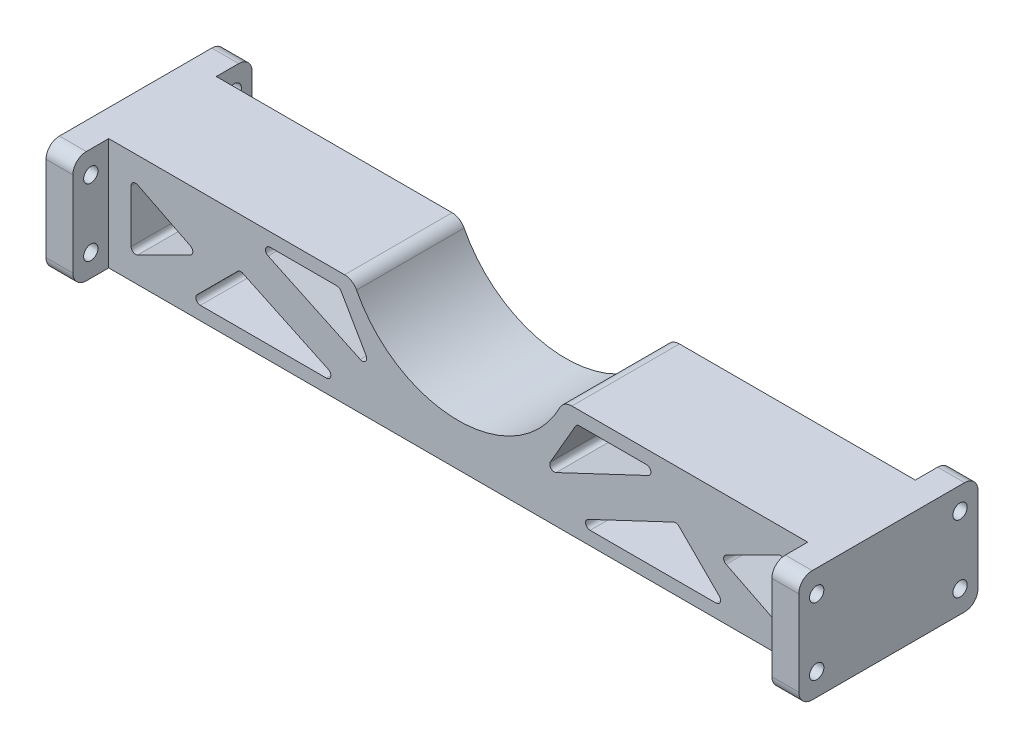
SolidWorks part; units mm, degrees
material "ABS"
ref_plane "前视基准面" through (0, 0, 0) normal (0, 0, 1) x (1, 0, 0)
ref_plane "上视基准面" through (0, 0, 0) normal (0, 1, 0) x (1, 0, 0)
ref_plane "右视基准面" through (0, 0, 0) normal (1, 0, 0) x (0, 0, -1)
other "Configuration Table"
sketch "草图1" plane through (0, 0, 0) normal (0, 0, 1) x (1, 0, 0)
  line L1 (0, 0) -> (168, 0)
  line L2 (0, 0) -> (0, -25)
  line L3 (0, -25) -> (168, -25)
  line L4 (168, 0) -> (168, -25)
  dimension "D1" = 168
  dimension "D2" = 25
extrude "凸台-拉伸1" add sketch "草图1" along normal blind 40
sketch "草图2" plane through (0, 0, 40) normal (0, 0, 1) x (1, 0, 0)
  line L1 (168, 0) -> (0, 0) construction
  line L2 (84, 10) -> (84, -25) construction
  line L3 (0, -25) -> (168, -25) construction
  circle A0 centre (84, 10) radius 25.5
  dimension "D2" = 51
  dimension "D3" = 10
extrude "切除-拉伸1" cut sketch "草图2" against normal through all
sketch "草图3" plane through (0, 0, 0) normal (0, 0, -1) x (-1, 0, 0)
  line L0 (-168, 0) -> (-107.4574, 0) construction
  line L1 (-162, 0) -> (-6, 0)
  line L2 (-162, 0) -> (-162, -25)
  line L3 (-162, -25) -> (-6, -25)
  line L4 (-6, 0) -> (-6, -25)
  line L5 (0, -25) -> (-168, -25) construction
  line L6 (-84, -15.5) -> (-84, 0) construction
  line L7 (0, 0) -> (0, -25) construction
  arc A0 (-107.4574, 0) -> (-60.5426, 0) centre (-84, 10) ccw construction
  dimension "D1" = 6
extrude "切除-拉伸2" cut sketch "草图3" against normal blind 8
sketch "草图4" plane through (0, 0, 40) normal (0, 0, 1) x (1, 0, 0)
  line L5 (162, 0) -> (107.4574, 0)
  line L6 (162, -25) -> (162, 0)
  line L7 (6, -25) -> (162, -25)
  line L8 (6, 0) -> (6, -25)
  line L9 (60.5426, 0) -> (6, 0)
  line L10 (162, 0) -> (107.4574, 0)
  line L11 (162, -25) -> (162, 0)
  line L12 (6, -25) -> (162, -25)
  line L13 (6, 0) -> (6, -25)
  line L15 (60.5426, 0) -> (6, 0)
  arc A1 (60.5426, 0) -> (107.4574, 0) centre (84, 10) ccw
  arc A3 (60.5426, 0) -> (107.4574, 0) centre (84, 10) ccw
  dimension "D1" = 0
extrude "切除-拉伸3" cut sketch "草图4" against normal blind 8
sketch "草图5" plane through (0, 0, 0) normal (-1, 0, 0) x (0, 0, 1)
  line L0 (4, 0) -> (4, -25) construction
  line L1 (40, 0) -> (0, 0) construction
  line L2 (40, -25) -> (0, -25) construction
  line L3 (0, 0) -> (0, -25) construction
  line L4 (20, 0) -> (20, -25) construction
  line L5 (4, -5) -> (36, -5) construction
  circle A0 centre (4, -5) radius 1.6
  circle A1 centre (4, -20) radius 1.6
  circle A2 centre (36, -20) radius 1.6
  circle A3 centre (36, -5) radius 1.6
  dimension "D2" = 3.2
  dimension "D3" = 5
  dimension "D4" = 5
  dimension "D1" = 4
extrude "切除-拉伸4" cut sketch "草图5" against normal through all
ref_plane "基准面1" through (0, -12.5, 0) normal (0, 1, 0) x (1, 0, 0)
sketch "草图6" plane through (0, -12.5, 0) normal (0, 1, 0) x (1, 0, 0)
  line L0 (6, 0) -> (6, -8)
  line L1 (6, -8) -> (36, -8)
  line L2 (6, -8) -> (60.5426, -8) construction
  line L3 (36, -8) -> (6, 0)
  line L4 (0, -20) -> (84, -20) construction
  line L5 (0, -40) -> (0, 0) construction
  line L6 (84, -20) -> (84, -32) construction
  line L7 (60.5426, -32) -> (107.4574, -32) construction
  line L8 (36, -32) -> (6, -40)
  line L9 (6, -32) -> (36, -32)
  line L10 (6, -40) -> (6, -32)
  line L11 (162, -40) -> (162, -32)
  line L12 (162, -32) -> (132, -32)
  line L13 (132, -32) -> (162, -40)
  line L14 (132, -8) -> (162, 0)
  line L15 (162, -8) -> (132, -8)
  line L16 (162, 0) -> (162, -8)
  dimension "D1" = 30
extrude "凸台-拉伸2" [suppressed] add sketch "草图6" along normal blind 2.5 and the other way blind 2.5
fillet "圆角1" [suppressed] radius 5
sketch "草图7" plane through (0, 0, 32) normal (0, 0, 1) x (1, 0, 0)
  line L0 (37.5426, -3) -> (57.5426, -3)
  line L1 (37.5426, -3) -> (65.0426, -15.9904)
  line L2 (57.5426, -3) -> (65.0426, -15.9904)
  line L3 (60.5426, 0) -> (6, 0) construction
  line L4 (24.0346, -22) -> (59.0346, -22)
  line L5 (59.0346, -22) -> (35.2635, -10.7711)
  line L6 (35.2635, -10.7711) -> (24.0346, -22)
  line L7 (6, -25) -> (162, -25) construction
  line L8 (11, -5) -> (11, -20)
  line L9 (11, -20) -> (26, -12.5)
  line L10 (26, -12.5) -> (11, -5)
  line L11 (26, -12.5) -> (11, -12.5) construction
  line L12 (11, -12.5) -> (6, -12.5) construction
  line L13 (6, 0) -> (6, -25) construction
  line L14 (84, -15.5) -> (84, -25) construction
  line L15 (157, -5) -> (157, -20)
  line L16 (142, -12.5) -> (157, -5)
  line L17 (157, -20) -> (142, -12.5)
  line L18 (132.7365, -10.7711) -> (143.9654, -22)
  line L19 (108.9654, -22) -> (132.7365, -10.7711)
  line L20 (143.9654, -22) -> (108.9654, -22)
  line L21 (110.4574, -3) -> (102.9574, -15.9904)
  line L22 (130.4574, -3) -> (102.9574, -15.9904)
  line L23 (130.4574, -3) -> (110.4574, -3)
  arc A0 (60.5426, 0) -> (107.4574, 0) centre (84, 10) ccw construction
  dimension "D1" = 3
  dimension "D2" = 60
  dimension "D3" = 3
  dimension "D4" = 20
  dimension "D5" = 15
  dimension "D6" = 3
  dimension "D7" = 8
  dimension "D8" = 45
  dimension "D9" = 35
  dimension "D10" = 15
  dimension "D11" = 5
  dimension "D12" = 15
extrude "切除-拉伸5" cut sketch "草图7" against normal through all
fillet "圆角2" radius 1 18 edges at (37.5426, -3, 20) (57.5426, -3, 20) (130.4574, -3, 20) (102.9574, -15.9904, 20) (110.4574, -3, 20) (157, -5, 20) (157, -20, 20) (142, -12.5, 20) (132.7365, -10.7711, 20) (143.9654, -22, 20) (108.9654, -22, 20) (35.2635, -10.7711, 20) (59.0346, -22, 20) (24.0346, -22, 20) (26, -12.5, 20) (11, -20, 20) (11, -5, 20) (65.0426, -15.9904, 20)
fillet "圆角3" radius 3 2 edges at (107.4574, 0, 20) (60.5426, 0, 20)
fillet "圆角4" radius 3 4 edges at (3, 0, 0) (3, -25, 40) (3, -25, 0) (3, 0, 40)
fillet "圆角5" radius 3 4 edges at (165, -25, 0) (165, -25, 40) (165, 0, 0) (165, 0, 40)
